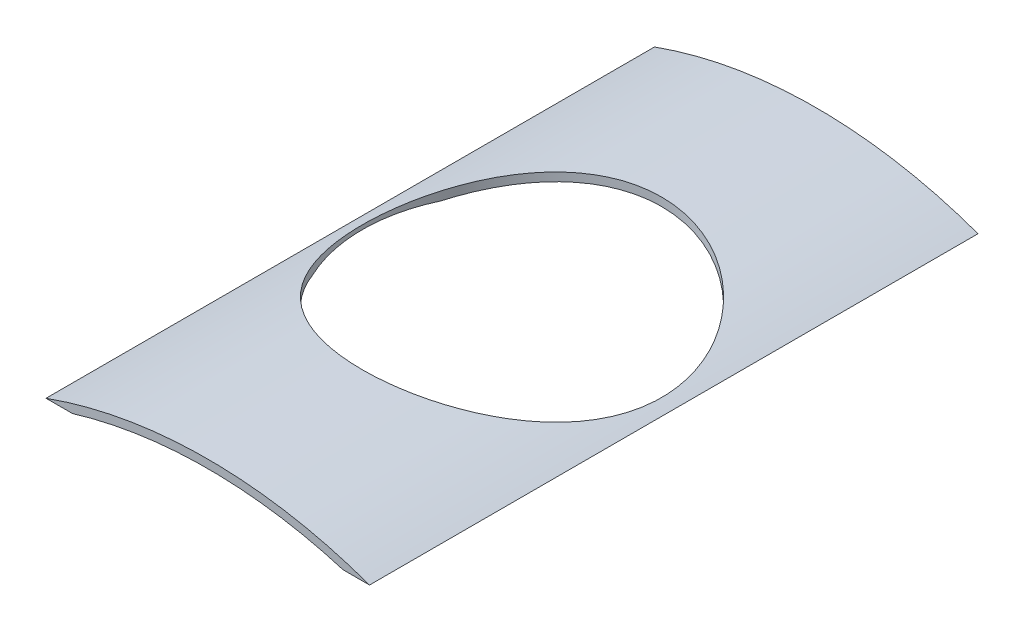
SolidWorks part; units mm, degrees
ref_plane "Plan de face" through (0, 0, 0) normal (0, 0, 1) x (1, 0, 0)
ref_plane "Plan de dessus" through (0, 0, 0) normal (0, 1, 0) x (1, 0, 0)
ref_plane "Plan de droite" through (0, 0, 0) normal (1, 0, 0) x (0, 0, -1)
sketch "Esquisse1" plane through (0, 0, 0) normal (0, 0, 1) x (1, 0, 0)
  line L5 (-52.5, 45) -> (52.5, 45)
  line L6 (-52.5, 45) -> (-52.5, -50)
  line L7 (-52.5, -50) -> (52.5, -50)
  line L8 (52.5, 45) -> (52.5, -50)
  circle A0 centre (0, 0) radius 47.8325
  circle A2 centre (0, 0) radius 47
  dimension "D1" = 95
  dimension "D3" = 52.5
  dimension "D2" = 105
  dimension "D4" = 50
extrude "Boss.-Extru.1" add sketch "Esquisse1" along normal blind 61 contours A2 L5 A0 region at (0, 47.507, 0)
sketch "Esquisse2" plane through (0, 45, 0) normal (0, -1, 0) x (1, 0, 0)
  line L0 (-13.5647, 0) -> (13.5647, 0) construction
  circle A0 centre (0, 30.5) radius 15
  dimension "D1" = 30.5
extrude "Enlèv. mat.-Extru.1" cut sketch "Esquisse2" against normal through all
